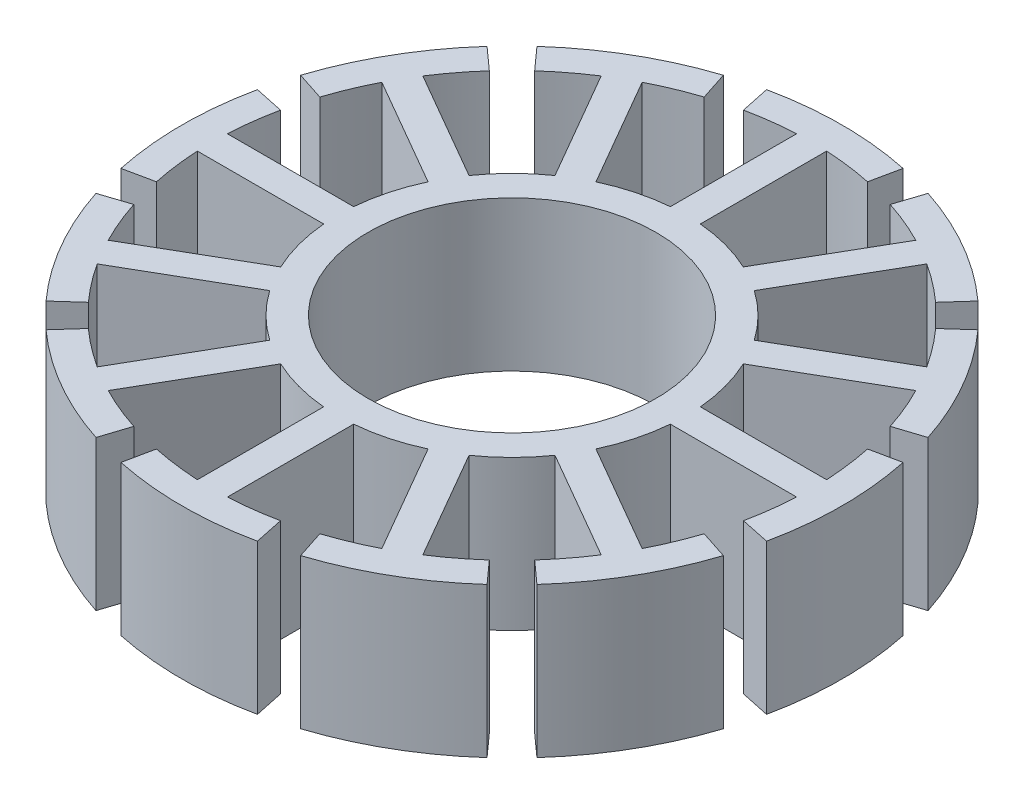
SolidWorks part; units mm, degrees
ref_plane "Front Plane" through (0, 0, 0) normal (0, 0, 1) x (1, 0, 0)
ref_plane "Top Plane" through (0, 0, 0) normal (0, 1, 0) x (1, 0, 0)
ref_plane "Right Plane" through (0, 0, 0) normal (1, 0, 0) x (0, 0, -1)
sketch "Sketch1" plane through (0, 0, 0) normal (0, 1, 0) x (1, 0, 0)
  line L0 (0, 11) -> (0, -11) construction
  line L1 (-0.5, 9.9875) -> (-0.5, 5.7784)
  line L2 (0.5, 9.9875) -> (0.5, 5.7784)
  line L3 (-2.0682, 9.7838) -> (-2.275, 10.7622)
  line L4 (2.0682, 9.7838) -> (2.275, 10.7622)
  line L5 (3.1008, 9.5071) -> (3.4109, 10.4578)
  line L6 (4.5607, 8.8994) -> (2.4562, 5.2542)
  line L7 (5.4268, 8.3994) -> (3.3222, 4.7542)
  line L8 (6.683, 7.4389) -> (7.3513, 8.1828)
  line L9 (7.4389, 6.683) -> (8.1828, 7.3513)
  line L10 (8.3994, 5.4268) -> (4.7542, 3.3222)
  line L11 (8.8994, 4.5607) -> (5.2542, 2.4562)
  line L12 (9.5071, 3.1008) -> (10.4578, 3.4109)
  line L13 (9.7838, 2.0682) -> (10.7622, 2.275)
  line L14 (9.9875, 0.5) -> (5.7784, 0.5)
  line L15 (9.9875, -0.5) -> (5.7784, -0.5)
  line L16 (9.7838, -2.0682) -> (10.7622, -2.275)
  line L17 (9.5071, -3.1008) -> (10.4578, -3.4109)
  line L18 (8.8994, -4.5607) -> (5.2542, -2.4562)
  line L19 (8.3994, -5.4268) -> (4.7542, -3.3222)
  line L20 (7.4389, -6.683) -> (8.1828, -7.3513)
  line L21 (6.683, -7.4389) -> (7.3513, -8.1828)
  line L22 (5.4268, -8.3994) -> (3.3222, -4.7542)
  line L23 (4.5607, -8.8994) -> (2.4562, -5.2542)
  line L24 (3.1008, -9.5071) -> (3.4109, -10.4578)
  line L25 (2.0682, -9.7838) -> (2.275, -10.7622)
  line L26 (0.5, -9.9875) -> (0.5, -5.7784)
  line L27 (-0.5, -9.9875) -> (-0.5, -5.7784)
  line L28 (-2.0682, -9.7838) -> (-2.275, -10.7622)
  line L29 (-3.1008, -9.5071) -> (-3.4109, -10.4578)
  line L30 (-4.5607, -8.8994) -> (-2.4562, -5.2542)
  line L31 (-5.4268, -8.3994) -> (-3.3222, -4.7542)
  line L32 (-6.683, -7.4389) -> (-7.3513, -8.1828)
  line L33 (-7.4389, -6.683) -> (-8.1828, -7.3513)
  line L34 (-8.3994, -5.4268) -> (-4.7542, -3.3222)
  line L35 (-8.8994, -4.5607) -> (-5.2542, -2.4562)
  line L36 (-9.5071, -3.1008) -> (-10.4578, -3.4109)
  line L37 (-9.7838, -2.0682) -> (-10.7622, -2.275)
  line L38 (-9.9875, -0.5) -> (-5.7784, -0.5)
  line L39 (-9.9875, 0.5) -> (-5.7784, 0.5)
  line L40 (-9.7838, 2.0682) -> (-10.7622, 2.275)
  line L41 (-9.5071, 3.1008) -> (-10.4578, 3.4109)
  line L42 (-8.8994, 4.5607) -> (-5.2542, 2.4562)
  line L43 (-8.3994, 5.4268) -> (-4.7542, 3.3222)
  line L44 (-7.4389, 6.683) -> (-8.1828, 7.3513)
  line L45 (-6.683, 7.4389) -> (-7.3513, 8.1828)
  line L46 (-5.4268, 8.3994) -> (-3.3222, 4.7542)
  line L47 (-4.5607, 8.8994) -> (-2.4562, 5.2542)
  line L48 (-3.1008, 9.5071) -> (-3.4109, 10.4578)
  circle A0 centre (0, 0) radius 4.8
  circle A1 centre (0, 0) radius 5.8
  circle A2 centre (0, 0) radius 11
  circle A3 centre (0, 0) radius 10
  point P16 (0, 0)
  point P17 (0, 0)
  point P106 (0, 0)
  point P107 (5.9286, 8.0531)
  point P108 (0, 0)
  dimension "D1" = 9.6
  dimension "D2" = 1
  dimension "D3" = 22
  dimension "D6" = 1
  dimension "D7" = 4.55
  dimension "D4" = 1
  dimension "D5" = 12
extrude "Boss-Extrude1" add sketch "Sketch1" along normal blind 5 contours A1 L0 A0 | L0 A1 A0 | L0 A3 L1 A1 | A3 L0 A1 L2 | A2 L0 A3 L4 | L0 A2 L3 A3 | L7 A3 L6 A1 | A3 L8 A2 L5 | L11 A3 L10 A1 | A3 L12 A2 L9 | L15 A3 L14 A1 | A3 L16 A2 L13 | L19 A3 L18 A1 | A3 L20 A2 L17 | L23 A3 L22 A1 | A3 L24 A2 L21 | L0 A1 L27 A3 | A1 L0 A3 L26 | A3 L0 A2 L25 | L0 A3 L28 A2 | L31 A3 L30 A1 | A3 L32 A2 L29 | L35 A3 L34 A1 | A3 L36 A2 L33 | L39 A3 L38 A1 | A3 L40 A2 L37 | L43 A3 L42 A1 | A3 L44 A2 L41 | L47 A3 L46 A1 | A3 L48 A2 L45 region at (1.0906, 0, -10.4321) region at (-1.0906, 0, -10.4321) region at (0.2501, 0, -7.8943) region at (-0.2501, 0, -7.8943) region at (0.2446, 0, -5.665) region at (-0.1297, 0, -5.3) region at (5.216, 0, -9.0345) region at (-5.216, 0, -9.0345) region at (3.9472, 0, -6.8367) region at (-3.9472, 0, -6.8367) region at (9.0345, 0, -5.216) region at (-9.0345, 0, -5.216) region at (0.2501, 0, 7.8943) region at (-0.2501, 0, 7.8943) region at (1.0906, 0, 10.4321) region at (-1.0906, 0, 10.4321) region at (6.8367, 0, -3.9472) region at (-6.8367, 0, -3.9472) region at (10.4321, 0, 0) region at (-10.4321, 0, 0) region at (-3.9472, 0, 6.8367) region at (3.9472, 0, 6.8367) region at (-5.216, 0, 9.0345) region at (5.216, 0, 9.0345) region at (7.8943, 0, 0) region at (-7.8943, 0, 0) region at (-9.0345, 0, 5.216) region at (-6.8367, 0, 3.9472) region at (6.8367, 0, 3.9472) region at (9.0345, 0, 5.216)
